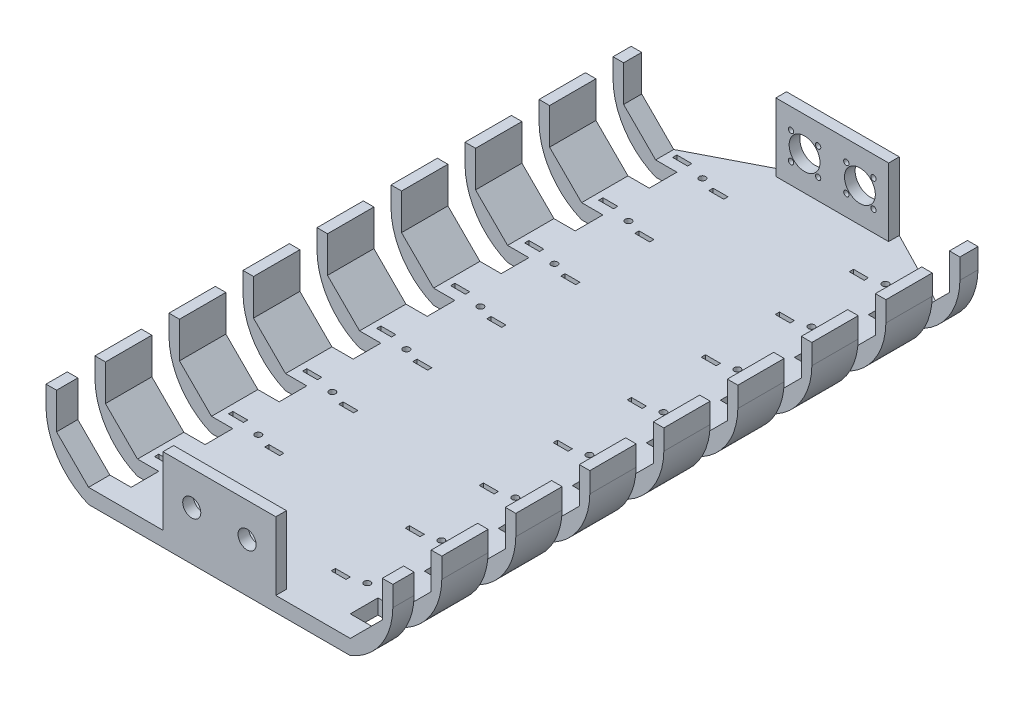
SolidWorks part; units mm, degrees
ref_plane "Front Plane" through (0, 0, 0) normal (0, 0, 1) x (1, 0, 0)
ref_plane "Top Plane" through (0, 0, 0) normal (0, 1, 0) x (1, 0, 0)
ref_plane "Right Plane" through (0, 0, 0) normal (1, 0, 0) x (0, 0, -1)
sketch "Sketch1" plane through (0, 0, 0) normal (0, 1, 0) x (1, 0, 0)
  line L0 (0, -135) -> (0, 135) construction
  line L1 (-13, 135) -> (-36, 135)
  line L2 (13, -135) -> (-13, -135)
  line L3 (13, -135) -> (13, 135) construction
  line L4 (13, 135) -> (-13, 135)
  line L5 (-13, -135) -> (-13, 135) construction
  line L8 (-36, 135) -> (-36, -135) construction
  line L9 (-36, -135) -> (-13, -135)
  line L10 (-36, 135) -> (-61.5, 135)
  line L11 (-61.5, 135) -> (-61.5, -135)
  line L12 (-61.5, -135) -> (-36, -135)
  line L13 (36, -135) -> (13, -135)
  line L14 (61.5, -135) -> (36, -135)
  line L15 (61.5, 135) -> (61.5, -135)
  line L16 (36, 135) -> (36, -135) construction
  line L17 (13, 135) -> (36, 135)
  line L18 (36, 135) -> (61.5, 135)
  point P0 (0, 0)
  point P4 (0, 0)
  dimension "D1" = 270
  dimension "D2" = 26
  dimension "D3" = 23
  dimension "D4" = 123
extrude "Boss-Extrude1" add sketch "Sketch1" along normal blind 7
sketch "Sketch2" plane through (0, 7, 0) normal (0, 1, 0) x (1, 0, 0)
  line L0 (61.5, -135) -> (61.5, 135) construction
  line L1 (-61.5, -135) -> (61.5, -135)
  line L2 (-61.5, -135) -> (-61.5, -130)
  line L3 (-61.5, -130) -> (61.5, -130)
  line L4 (61.5, -135) -> (61.5, -130)
  line L21 (-26.5, 130) -> (-26.5, -130) construction
  dimension "D1" = 5
extrude "Boss-Extrude2" add sketch "Sketch2" along normal blind 32
sketch "Sketch3" plane through (0, 0, 135) normal (0, 0, 1) x (1, 0, 0)
  line L0 (0, 39) -> (0, 0) construction
  line L2 (-61.5, 39) -> (-61.5, 7) construction
  line L3 (-61.5, 39) -> (61.5, 39) construction
  line L5 (-61.5, 39) -> (-61.5, 0) construction
  line L6 (-61.5, 23) -> (61.5, 23) construction
  line L7 (61.5, 39) -> (61.5, 0) construction
  circle A0 centre (-13, 23) radius 4.25
  circle A1 centre (13, 23) radius 4.25
  dimension "D1" = 8.5
  dimension "D2" = 8.5
  dimension "D3" = 26
  dimension "D4" = 13
  dimension "D5" = 32
  dimension "D6" = 16
sketch "Sketch9" plane through (0, 0, -135) normal (0, 0, -1) x (-1, 0, 0)
  line L1 (-61.5, 7) -> (61.5, 7)
  line L2 (-61.5, 7) -> (-61.5, 0)
  line L3 (-61.5, 0) -> (61.5, 0)
  line L4 (61.5, 7) -> (61.5, 0)
extrude "Boss-Extrude4" add sketch "Sketch9" along normal blind 5
sketch "Sketch13" plane through (0, 0, 135) normal (0, 0, 1) x (1, 0, 0)
  line L0 (-61.5, 39) -> (-61.5, 7)
  line L1 (-61.5, 39) -> (-61.5, 0) construction
  line L2 (-61.5, 39) -> (-26.5, 39)
  line L3 (-61.5, 39) -> (61.5, 39) construction
  line L4 (-26.5, 39) -> (-26.5, 7)
  line L5 (-26.5, 7) -> (-61.5, 7)
  line L6 (0, 39) -> (0, 5.5161) construction
  line L7 (26.5, 39) -> (26.5, 7)
  line L8 (61.5, 39) -> (26.5, 39)
  line L9 (61.5, 39) -> (61.5, 7)
  line L10 (26.5, 7) -> (61.5, 7)
  dimension "D1" = 32
  dimension "D2" = 35
extrude "Cut-Extrude5" cut sketch "Sketch13" against normal blind 11
sketch "Sketch14" plane through (0, 0, 135) normal (0, 0, 1) x (1, 0, 0)
  line L0 (0, 39) -> (0, 0) construction
  line L1 (-26.5, 39) -> (26.5, 39) construction
  line L2 (-81.5, 39) -> (0, 39) construction
  line L3 (-61.5, 0) -> (-81.5, 20) construction
  line L5 (-76.55, 22.05) -> (-61.5, 7)
  line L6 (-61.5, 0) -> (61.5, 0) construction
  line L7 (-61.5, 7) -> (-61.5, 0)
  line L12 (-81.5, 20) -> (-81.5, 39) construction
  line L13 (-81.5, 39) -> (-76.55, 39)
  line L14 (-76.55, 39) -> (-76.55, 22.05)
  line L21 (-61.5, 7) -> (-61.5, 39) construction
  line L22 (-81.5, 39) -> (-81.5, 29.5)
  line L23 (81.5, 39) -> (76.55, 39)
  line L24 (76.55, 39) -> (76.55, 22.05)
  line L25 (76.55, 22.05) -> (61.5, 7)
  line L26 (61.5, 7) -> (61.5, 0)
  line L27 (81.5, 39) -> (81.5, 29.5)
  arc A0 (-61.5, 0) -> (-81.5, 29.5) centre (-49.0062, 30) cw
  arc A1 (61.5, 0) -> (81.5, 29.5) centre (49.0062, 30) ccw
  dimension "D1" = 28.2843
  dimension "D2" = 45
  dimension "D3" = 4.95
  dimension "D4" = 20
  dimension "D5" = 4.9497
  dimension "D6" = 21.2839
  dimension "D7" = 30
  dimension "D8" = 9.5
extrude "Boss-Extrude10" add sketch "Sketch14" against normal blind 275
sketch "Sketch17" plane through (0, 7, 0) normal (0, 1, 0) x (1, 0, 0)
  line L0 (-26.5, 130) -> (26.5, 130) construction
  line L1 (0, 130) -> (0, 161) construction
  line L2 (-26.5, -135) -> (-26.5, 161) construction
  line L3 (26.5, -135) -> (26.5, 161) construction
  line L4 (26.5, 161) -> (-26.5, 161) construction
  line L5 (0, 161) -> (0, 226) construction
  line L6 (-61.5, 140) -> (-26.5, 226)
  line L7 (-26.5, 226) -> (0, 226)
  line L8 (0, 226) -> (26.5, 226)
  line L9 (26.5, 226) -> (61.5, 140)
  line L10 (26.5, 161) -> (26.5, 226) construction
  line L11 (-26.5, 161) -> (-26.5, 226) construction
  line L12 (-61.5, 140) -> (61.5, 140)
  line L13 (-61.5, 140) -> (61.5, 140) construction
  dimension "D1" = 31
  dimension "D2" = 296
  dimension "D3" = 90
  dimension "D4" = 65
  dimension "D5" = 10
extrude "Boss-Extrude13" add sketch "Sketch17" against normal blind 7 contours L12 L9 L8 L7 L6
sketch "Sketch18" plane through (0, 7, 0) normal (0, 1, 0) x (1, 0, 0)
  line L0 (-26.5, 127) -> (26.5, 127) construction
  line L1 (0, 127) -> (0, 158) construction
  line L2 (-26.5, 135) -> (-26.5, 158) construction
  line L3 (26.5, 132) -> (26.5, 158) construction
  line L4 (-26.5, 158) -> (-26.5, 153)
  line L5 (-26.5, 153) -> (26.5, 153)
  line L6 (26.5, 153) -> (26.5, 158)
  line L7 (26.5, 158) -> (-26.5, 158)
  line L8 (-61.5, 140) -> (-61.5, -135) construction
  line L9 (76.55, 140) -> (61.5, 140) construction
  dimension "D1" = 31
  dimension "D2" = 5
  dimension "D3" = 35
  dimension "D4" = 53
  dimension "D5" = 13
extrude "Boss-Extrude14" add sketch "Sketch18" along normal blind 32
extrude "Cut-Extrude8" cut sketch "Sketch3" against normal blind 334
sketch "Sketch19" plane through (0, 0, -153) normal (0, 0, 1) x (1, 0, 0)
  line L0 (0, 39) -> (0, 0) construction
  line L1 (-26.5, 39) -> (26.5, 39) construction
  line L3 (-6.636, 16.636) -> (-19.364, 16.636) construction
  line L4 (-6.636, 16.636) -> (-6.636, 29.364) construction
  line L5 (-6.636, 29.364) -> (-19.364, 29.364) construction
  line L6 (-19.364, 16.636) -> (-19.364, 29.364) construction
  line L7 (-6.636, 16.636) -> (-19.364, 29.364) construction
  line L8 (-6.636, 29.364) -> (-19.364, 16.636) construction
  circle A0 centre (-13, 23) radius 7.25
  circle A1 centre (-6.636, 16.636) radius 1.25
  circle A2 centre (-6.636, 29.364) radius 1.25
  circle A3 centre (-19.364, 29.364) radius 1.25
  circle A4 centre (-19.364, 16.636) radius 1.25
  circle A5 centre (13, 23) radius 7.25
  circle A6 centre (19.364, 16.636) radius 1.25
  circle A7 centre (6.636, 16.636) radius 1.25
  circle A8 centre (6.636, 29.364) radius 1.25
  circle A9 centre (19.364, 29.364) radius 1.25
  dimension "D1" = 14.5
  dimension "D4" = 2.5
  dimension "D5" = 2.5
  dimension "D6" = 2.5
  dimension "D7" = 2.5
  dimension "D2" = 18
  dimension "D3" = 18
  dimension "D8" = 12.7279
extrude "Cut-Extrude9" cut sketch "Sketch19" against normal blind 334
sketch "Sketch29" plane through (0, 7, 0) normal (0, 1, 0) x (1, 0, 0)
  line L0 (-61.5, 140) -> (-26.5, 158)
  line L1 (-26.5, 158) -> (26.5, 158)
  line L2 (26.5, 158) -> (61.5, 140)
  line L3 (61.5, 140) -> (26.5, 226)
  line L4 (26.5, 226) -> (-26.5, 226)
  line L5 (-26.5, 226) -> (-61.5, 140)
extrude "Cut-Extrude13" cut sketch "Sketch29" against normal blind 19
sketch "Sketch32" plane through (0, 7, 0) normal (0, 1, 0) x (1, 0, 0)
  line L0 (-61.5, 137.5) -> (-55, 137.5) construction
  line L1 (-61.5, 140) -> (-26.5, 140) construction
  line L3 (-61.5, 140) -> (-61.5, 130) construction
  line L4 (0, 158) -> (0, -135) construction
  line L5 (26.5, 158) -> (-26.5, 158) construction
  line L6 (-26.5, -135) -> (26.5, -135) construction
  line L7 (-61.5, 130) -> (-26.5, 130) construction
  line L8 (-81.5, 131.5) -> (-51.5, 131.5)
  line L9 (-26.5, 140) -> (-26.5, 130) construction
  line L10 (-81.5, 131.5) -> (-81.5, 118.5)
  line L11 (-51.5, 136.5) -> (-58.5, 136.5)
  line L12 (-51.5, 136.5) -> (-51.5, 138.5)
  line L13 (-51.5, 138.5) -> (-58.5, 138.5)
  line L14 (-58.5, 136.5) -> (-58.5, 138.5)
  line L15 (-51.5, 136.5) -> (-58.5, 138.5) construction
  line L16 (-51.5, 138.5) -> (-58.5, 136.5) construction
  line L17 (-29.5, 131.5) -> (-36.5, 131.5)
  line L18 (-29.5, 131.5) -> (-29.5, 133.5)
  line L19 (-29.5, 133.5) -> (-36.5, 133.5)
  line L20 (-36.5, 131.5) -> (-36.5, 133.5)
  line L21 (-29.5, 131.5) -> (-36.5, 133.5) construction
  line L22 (-29.5, 133.5) -> (-36.5, 131.5) construction
  line L23 (-81.5, 118.5) -> (-51.5, 118.5)
  line L24 (-51.5, 131.5) -> (-51.5, 118.5)
  line L25 (-81.5, 96.7143) -> (-81.5, 83.7143)
  line L26 (-81.5, 96.7143) -> (-51.5, 96.7143)
  line L27 (-51.5, 96.7143) -> (-51.5, 83.7143)
  line L28 (-81.5, 83.7143) -> (-51.5, 83.7143)
  line L29 (-51.5, 101.7143) -> (-51.5, 103.7143)
  line L30 (-51.5, 101.7143) -> (-58.5, 101.7143)
  line L31 (-58.5, 101.7143) -> (-58.5, 103.7143)
  line L32 (-51.5, 103.7143) -> (-58.5, 103.7143)
  line L33 (-29.5, 96.7143) -> (-29.5, 98.7143)
  line L34 (-29.5, 96.7143) -> (-36.5, 96.7143)
  line L35 (-36.5, 96.7143) -> (-36.5, 98.7143)
  line L36 (-29.5, 98.7143) -> (-36.5, 98.7143)
  line L37 (-81.5, 61.9286) -> (-81.5, 48.9286)
  line L38 (-81.5, 61.9286) -> (-51.5, 61.9286)
  line L39 (-51.5, 61.9286) -> (-51.5, 48.9286)
  line L40 (-81.5, 48.9286) -> (-51.5, 48.9286)
  line L41 (-51.5, 66.9286) -> (-51.5, 68.9286)
  line L42 (-51.5, 66.9286) -> (-58.5, 66.9286)
  line L43 (-58.5, 66.9286) -> (-58.5, 68.9286)
  line L44 (-51.5, 68.9286) -> (-58.5, 68.9286)
  line L45 (-29.5, 61.9286) -> (-29.5, 63.9286)
  line L46 (-29.5, 61.9286) -> (-36.5, 61.9286)
  line L47 (-36.5, 61.9286) -> (-36.5, 63.9286)
  line L48 (-29.5, 63.9286) -> (-36.5, 63.9286)
  line L49 (-81.5, 27.1429) -> (-81.5, 14.1429)
  line L50 (-81.5, 27.1429) -> (-51.5, 27.1429)
  line L51 (-51.5, 27.1429) -> (-51.5, 14.1429)
  line L52 (-81.5, 14.1429) -> (-51.5, 14.1429)
  line L53 (-51.5, 32.1429) -> (-51.5, 34.1429)
  line L54 (-51.5, 32.1429) -> (-58.5, 32.1429)
  line L55 (-58.5, 32.1429) -> (-58.5, 34.1429)
  line L56 (-51.5, 34.1429) -> (-58.5, 34.1429)
  line L57 (-29.5, 27.1429) -> (-29.5, 29.1429)
  line L58 (-29.5, 27.1429) -> (-36.5, 27.1429)
  line L59 (-36.5, 27.1429) -> (-36.5, 29.1429)
  line L60 (-29.5, 29.1429) -> (-36.5, 29.1429)
  line L61 (-81.5, -7.6429) -> (-81.5, -20.6429)
  line L62 (-81.5, -7.6429) -> (-51.5, -7.6429)
  line L63 (-51.5, -7.6429) -> (-51.5, -20.6429)
  line L64 (-81.5, -20.6429) -> (-51.5, -20.6429)
  line L65 (-51.5, -2.6429) -> (-51.5, -0.6429)
  line L66 (-51.5, -2.6429) -> (-58.5, -2.6429)
  line L67 (-58.5, -2.6429) -> (-58.5, -0.6429)
  line L68 (-51.5, -0.6429) -> (-58.5, -0.6429)
  line L69 (-29.5, -7.6429) -> (-29.5, -5.6429)
  line L70 (-29.5, -7.6429) -> (-36.5, -7.6429)
  line L71 (-36.5, -7.6429) -> (-36.5, -5.6429)
  line L72 (-29.5, -5.6429) -> (-36.5, -5.6429)
  line L73 (-81.5, -42.4286) -> (-81.5, -55.4286)
  line L74 (-81.5, -42.4286) -> (-51.5, -42.4286)
  line L75 (-51.5, -42.4286) -> (-51.5, -55.4286)
  line L76 (-81.5, -55.4286) -> (-51.5, -55.4286)
  line L77 (-51.5, -37.4286) -> (-51.5, -35.4286)
  line L78 (-51.5, -37.4286) -> (-58.5, -37.4286)
  line L79 (-58.5, -37.4286) -> (-58.5, -35.4286)
  line L80 (-51.5, -35.4286) -> (-58.5, -35.4286)
  line L81 (-29.5, -42.4286) -> (-29.5, -40.4286)
  line L82 (-29.5, -42.4286) -> (-36.5, -42.4286)
  line L83 (-36.5, -42.4286) -> (-36.5, -40.4286)
  line L84 (-29.5, -40.4286) -> (-36.5, -40.4286)
  line L85 (-81.5, -77.2143) -> (-81.5, -90.2143)
  line L86 (-81.5, -77.2143) -> (-51.5, -77.2143)
  line L87 (-51.5, -77.2143) -> (-51.5, -90.2143)
  line L88 (-81.5, -90.2143) -> (-51.5, -90.2143)
  line L89 (-51.5, -72.2143) -> (-51.5, -70.2143)
  line L90 (-51.5, -72.2143) -> (-58.5, -72.2143)
  line L91 (-58.5, -72.2143) -> (-58.5, -70.2143)
  line L92 (-51.5, -70.2143) -> (-58.5, -70.2143)
  line L93 (-29.5, -77.2143) -> (-29.5, -75.2143)
  line L94 (-29.5, -77.2143) -> (-36.5, -77.2143)
  line L95 (-36.5, -77.2143) -> (-36.5, -75.2143)
  line L96 (-29.5, -75.2143) -> (-36.5, -75.2143)
  line L97 (-81.5, -112) -> (-81.5, -125)
  line L98 (-81.5, -112) -> (-51.5, -112)
  line L99 (-51.5, -112) -> (-51.5, -125)
  line L100 (-81.5, -125) -> (-51.5, -125)
  line L101 (-51.5, -107) -> (-51.5, -105)
  line L102 (-51.5, -107) -> (-58.5, -107)
  line L103 (-58.5, -107) -> (-58.5, -105)
  line L104 (-51.5, -105) -> (-58.5, -105)
  line L105 (-29.5, -112) -> (-29.5, -110)
  line L106 (-29.5, -112) -> (-36.5, -112)
  line L107 (-36.5, -112) -> (-36.5, -110)
  line L108 (-29.5, -110) -> (-36.5, -110)
  line L109 (-26.5, -130) -> (-26.5, -125) construction
  line L110 (-26.5, -125) -> (-51.5, -125) construction
  line L111 (26.5, -125) -> (51.5, -125) construction
  line L112 (26.5, -130) -> (26.5, -125) construction
  line L113 (29.5, 133.5) -> (36.5, 131.5) construction
  line L114 (29.5, 131.5) -> (36.5, 133.5) construction
  line L115 (51.5, 138.5) -> (58.5, 136.5) construction
  line L116 (51.5, 136.5) -> (58.5, 138.5) construction
  line L117 (26.5, 140) -> (26.5, 130) construction
  line L118 (61.5, 130) -> (26.5, 130) construction
  line L119 (61.5, 140) -> (61.5, 130) construction
  line L120 (61.5, 140) -> (26.5, 140) construction
  line L121 (61.5, 137.5) -> (55, 137.5) construction
  line L122 (29.5, -110) -> (36.5, -110)
  line L123 (36.5, -112) -> (36.5, -110)
  line L124 (29.5, -112) -> (36.5, -112)
  line L125 (29.5, -112) -> (29.5, -110)
  line L126 (51.5, -105) -> (58.5, -105)
  line L127 (58.5, -107) -> (58.5, -105)
  line L128 (51.5, -107) -> (58.5, -107)
  line L129 (51.5, -107) -> (51.5, -105)
  line L130 (81.5, -125) -> (51.5, -125)
  line L131 (51.5, -112) -> (51.5, -125)
  line L132 (81.5, -112) -> (51.5, -112)
  line L133 (81.5, -112) -> (81.5, -125)
  line L134 (29.5, -75.2143) -> (36.5, -75.2143)
  line L135 (36.5, -77.2143) -> (36.5, -75.2143)
  line L136 (29.5, -77.2143) -> (36.5, -77.2143)
  line L137 (29.5, -77.2143) -> (29.5, -75.2143)
  line L138 (51.5, -70.2143) -> (58.5, -70.2143)
  line L139 (58.5, -72.2143) -> (58.5, -70.2143)
  line L140 (51.5, -72.2143) -> (58.5, -72.2143)
  line L141 (51.5, -72.2143) -> (51.5, -70.2143)
  line L142 (81.5, -90.2143) -> (51.5, -90.2143)
  line L143 (51.5, -77.2143) -> (51.5, -90.2143)
  line L144 (81.5, -77.2143) -> (51.5, -77.2143)
  line L145 (81.5, -77.2143) -> (81.5, -90.2143)
  line L146 (29.5, -40.4286) -> (36.5, -40.4286)
  line L147 (36.5, -42.4286) -> (36.5, -40.4286)
  line L148 (29.5, -42.4286) -> (36.5, -42.4286)
  line L149 (29.5, -42.4286) -> (29.5, -40.4286)
  line L150 (51.5, -35.4286) -> (58.5, -35.4286)
  line L151 (58.5, -37.4286) -> (58.5, -35.4286)
  line L152 (51.5, -37.4286) -> (58.5, -37.4286)
  line L153 (51.5, -37.4286) -> (51.5, -35.4286)
  line L154 (81.5, -55.4286) -> (51.5, -55.4286)
  line L155 (51.5, -42.4286) -> (51.5, -55.4286)
  line L156 (81.5, -42.4286) -> (51.5, -42.4286)
  line L157 (81.5, -42.4286) -> (81.5, -55.4286)
  line L158 (29.5, -5.6429) -> (36.5, -5.6429)
  line L159 (36.5, -7.6429) -> (36.5, -5.6429)
  line L160 (29.5, -7.6429) -> (36.5, -7.6429)
  line L161 (29.5, -7.6429) -> (29.5, -5.6429)
  line L162 (51.5, -0.6429) -> (58.5, -0.6429)
  line L163 (58.5, -2.6429) -> (58.5, -0.6429)
  line L164 (51.5, -2.6429) -> (58.5, -2.6429)
  line L165 (51.5, -2.6429) -> (51.5, -0.6429)
  line L166 (81.5, -20.6429) -> (51.5, -20.6429)
  line L167 (51.5, -7.6429) -> (51.5, -20.6429)
  line L168 (81.5, -7.6429) -> (51.5, -7.6429)
  line L169 (81.5, -7.6429) -> (81.5, -20.6429)
  line L170 (29.5, 29.1429) -> (36.5, 29.1429)
  line L171 (36.5, 27.1429) -> (36.5, 29.1429)
  line L172 (29.5, 27.1429) -> (36.5, 27.1429)
  line L173 (29.5, 27.1429) -> (29.5, 29.1429)
  line L174 (51.5, 34.1429) -> (58.5, 34.1429)
  line L175 (58.5, 32.1429) -> (58.5, 34.1429)
  line L176 (51.5, 32.1429) -> (58.5, 32.1429)
  line L177 (51.5, 32.1429) -> (51.5, 34.1429)
  line L178 (81.5, 14.1429) -> (51.5, 14.1429)
  line L179 (51.5, 27.1429) -> (51.5, 14.1429)
  line L180 (81.5, 27.1429) -> (51.5, 27.1429)
  line L181 (81.5, 27.1429) -> (81.5, 14.1429)
  line L182 (29.5, 63.9286) -> (36.5, 63.9286)
  line L183 (36.5, 61.9286) -> (36.5, 63.9286)
  line L184 (29.5, 61.9286) -> (36.5, 61.9286)
  line L185 (29.5, 61.9286) -> (29.5, 63.9286)
  line L186 (51.5, 68.9286) -> (58.5, 68.9286)
  line L187 (58.5, 66.9286) -> (58.5, 68.9286)
  line L188 (51.5, 66.9286) -> (58.5, 66.9286)
  line L189 (51.5, 66.9286) -> (51.5, 68.9286)
  line L190 (81.5, 48.9286) -> (51.5, 48.9286)
  line L191 (51.5, 61.9286) -> (51.5, 48.9286)
  line L192 (81.5, 61.9286) -> (51.5, 61.9286)
  line L193 (81.5, 61.9286) -> (81.5, 48.9286)
  line L194 (29.5, 98.7143) -> (36.5, 98.7143)
  line L195 (36.5, 96.7143) -> (36.5, 98.7143)
  line L196 (29.5, 96.7143) -> (36.5, 96.7143)
  line L197 (29.5, 96.7143) -> (29.5, 98.7143)
  line L198 (51.5, 103.7143) -> (58.5, 103.7143)
  line L199 (58.5, 101.7143) -> (58.5, 103.7143)
  line L200 (51.5, 101.7143) -> (58.5, 101.7143)
  line L201 (51.5, 101.7143) -> (51.5, 103.7143)
  line L202 (81.5, 83.7143) -> (51.5, 83.7143)
  line L203 (51.5, 96.7143) -> (51.5, 83.7143)
  line L204 (81.5, 96.7143) -> (51.5, 96.7143)
  line L205 (81.5, 96.7143) -> (81.5, 83.7143)
  line L206 (51.5, 131.5) -> (51.5, 118.5)
  line L207 (81.5, 118.5) -> (51.5, 118.5)
  line L208 (36.5, 131.5) -> (36.5, 133.5)
  line L209 (29.5, 133.5) -> (36.5, 133.5)
  line L210 (29.5, 131.5) -> (29.5, 133.5)
  line L211 (29.5, 131.5) -> (36.5, 131.5)
  line L212 (58.5, 136.5) -> (58.5, 138.5)
  line L213 (51.5, 138.5) -> (58.5, 138.5)
  line L214 (51.5, 136.5) -> (51.5, 138.5)
  line L215 (51.5, 136.5) -> (58.5, 136.5)
  line L216 (81.5, 131.5) -> (81.5, 118.5)
  line L217 (81.5, 131.5) -> (51.5, 131.5)
  line L218 (-81.5, 140) -> (-81.5, -135) construction
  circle A0 centre (-43, 135) radius 1.5
  circle A1 centre (-43, 100.2143) radius 1.5
  circle A2 centre (-43, 65.4286) radius 1.5
  circle A3 centre (-43, 30.6429) radius 1.5
  circle A4 centre (-43, -4.1429) radius 1.5
  circle A5 centre (-43, -38.9286) radius 1.5
  circle A6 centre (-43, -73.7143) radius 1.5
  circle A7 centre (-43, -108.5) radius 1.5
  circle A8 centre (43, -108.5) radius 1.5
  circle A9 centre (43, -73.7143) radius 1.5
  circle A10 centre (43, -38.9286) radius 1.5
  circle A11 centre (43, -4.1429) radius 1.5
  circle A12 centre (43, 30.6429) radius 1.5
  circle A13 centre (43, 65.4286) radius 1.5
  circle A14 centre (43, 100.2143) radius 1.5
  circle A15 centre (43, 135) radius 1.5
  point P21 (-33, 132.5)
  point P252 (33, 132.5)
  dimension "D7" = 3
  dimension "D1" = 10
  dimension "D2" = 35
  dimension "D3" = 2
  dimension "D4" = 7
  dimension "D5" = 3
  dimension "D6" = 2.5
  dimension "D8" = 18.5
  dimension "D9" = 5
  dimension "D10" = 3
  dimension "D11" = 2.5
  dimension "D12" = 7
  dimension "D13" = 2
  dimension "D14" = 5
  dimension "D15" = 13
  dimension "D17" = 5
  dimension "D16" = 8
extrude "Cut-Extrude16" cut sketch "Sketch32" against normal through all both and the other way through all
